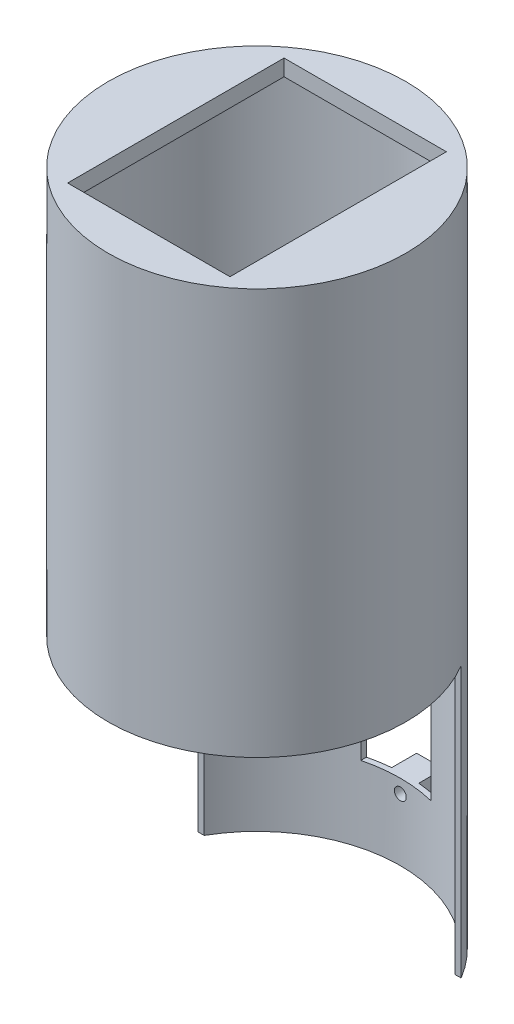
SolidWorks part; units mm, degrees
ref_plane "前基準面" through (0, 0, 0) normal (0, 0, 1) x (1, 0, 0)
ref_plane "上基準面" through (0, 0, 0) normal (0, 1, 0) x (1, 0, 0)
ref_plane "右基準面" through (0, 0, 0) normal (1, 0, 0) x (0, 0, -1)
sketch "草圖1" plane through (0, 0, 0) normal (0, 1, 0) x (1, 0, 0)
  circle A0 centre (0, 0) radius 27.5
  circle A1 centre (0, 0) radius 26.5
  dimension "D1" = 55
  dimension "D2" = 53
extrude "填料-伸長1" add sketch "草圖1" along normal blind 75 and the other way blind 50 contours A0
ref_plane "平面3" through (0, -10, 0) normal (0, 1, 0) x (1, 0, 0)
sketch "草圖8" plane through (0, 0, 0) normal (0, 1, 0) x (1, 0, 0)
  line L0 (0, 27.5) -> (0, -27.5) construction
  line L1 (14, 20.8205) -> (-14, 20.8205)
  line L2 (-14, 20.8205) -> (-14, -20.1795)
  line L3 (-14, -20.1795) -> (14, -20.1795)
  line L4 (14, 20.8205) -> (14, -20.1795)
  circle A1 centre (0, 0) radius 27.5 construction
  point P11 (0, -20.1795)
  point P12 (0, 20.8205)
  dimension "D1" = 28
  dimension "D2" = 41
sketch "草圖10" plane through (0, 75, 0) normal (0, 1, 0) x (1, 0, 0)
  line L0 (0, 27.5) -> (0, -27.5) construction
  line L10 (-27.5, 0) -> (27.5, 0) construction
  line L11 (-30.25, 0) -> (30.25, 0) construction
  line L12 (-15, 20) -> (-15, -20)
  line L13 (-15, 20) -> (15, 20)
  line L15 (-15, -20) -> (15, -20)
  line L16 (15, 20) -> (15, -20)
  circle A0 centre (0, 0) radius 27.5 construction
  dimension "D2" = 40
extrude "除料-伸長8" cut sketch "草圖10" against normal blind 45.1
ref_plane "平面4" through (0, 0, -37) normal (0, 0, 1) x (1, 0, 0)
extrude "除料-伸長9" cut sketch "草圖10<2>" against normal blind 113 and the other way blind 10
sketch "草圖10<2>" plane through (0, 75, 0) normal (0, 1, 0) x (1, 0, 0) same geometry as "草圖10"
sketch "草圖11" plane through (0, 0, 0) normal (0, 1, 0) x (1, 0, 0)
  line L0 (23.588, 14.1371) -> (-24.132, 13.1869)
  arc A0 (-24.132, 13.1869) -> (23.588, 14.1371) centre (0, 0) ccw
  circle A1 centre (0, 0) radius 27.5 construction
extrude "除料-伸長10" cut sketch "草圖11" against normal blind 54
sketch "草圖12" plane through (0, 0, 0) normal (0, 1, 0) x (1, 0, 0)
  line L0 (0, 27.5) -> (0, -27.5) construction
  circle A0 centre (0, 0) radius 26.5
  dimension "D1" = 53
extrude "除料-伸長11" cut sketch "草圖12" against normal blind 55 and the other way blind 72
sketch "草圖13" plane through (0, 0, 0) normal (0, 0, 1) x (1, 0, 0)
  line L0 (0, 0) -> (0, -54.6017) construction
  line L1 (-24.132, -25) -> (22.4286, -25) construction
  line L2 (-24.132, -50) -> (-24.132, 0) construction
  line L3 (22.4286, -50) -> (22.4286, 0) construction
  line L5 (-6.5, -12.5) -> (6.5, -12.5)
  line L6 (-6.5, -12.5) -> (-6.5, -36)
  line L7 (-6.5, -36) -> (6.5, -36)
  line L8 (6.5, -12.5) -> (6.5, -36)
  dimension "D1" = 13
  dimension "D2" = 23.5
  dimension "D3" = 6.5
  dimension "D4" = 12.5
extrude "除料-伸長12" cut sketch "草圖13" against normal blind 54
ref_plane "平面5" through (0, 0, -28) normal (0, 0, 1) x (1, 0, 0)
sketch "草圖14" plane through (0, 0, -28) normal (0, 0, 1) x (1, 0, 0)
  line L0 (0, -12.5) -> (0, -38.2336) construction
  line L1 (-6.5, -12.5) -> (6.5, -12.5) construction
  line L7 (6.5, -24.25) -> (-6.5, -24.25) construction
  line L8 (6.5, -12.5) -> (6.5, -36) construction
  line L9 (-6.5, -36) -> (-6.5, -12.5) construction
  line L10 (2.5, -36) -> (-2.5, -36)
  line L11 (2.5, -7.5) -> (-2.5, -7.5)
  line L12 (2.5, -7.5) -> (2.5, -12.5)
  line L13 (2.5, -12.5) -> (-2.5, -12.5)
  line L14 (-2.5, -7.5) -> (-2.5, -12.5)
  line L15 (-2.5, -41) -> (-2.5, -36)
  line L16 (2.5, -41) -> (-2.5, -41)
  line L17 (2.5, -41) -> (2.5, -36)
  dimension "D1" = 5
  dimension "D2" = 5
  dimension "D3" = 2.5
extrude "填料-伸長2" add sketch "草圖14" against normal blind 4 and the other way blind 1
sketch "草圖15" plane through (0, 0, -28) normal (0, 0, 1) x (1, 0, 0)
  line L0 (6.5, -24.25) -> (-6.5, -24.25) construction
  line L3 (6.5, -12.5) -> (6.5, -36) construction
  line L4 (-6.5, -36) -> (-6.5, -12.5) construction
  line L5 (30.25, -10) -> (-30.25, -10) construction
  circle A2 centre (0, -10) radius 1.1
  circle A3 centre (0, -38.5) radius 1.1
  dimension "D1" = 2.2
extrude "除料-伸長13" cut sketch "草圖15" against normal blind 5 and the other way blind 4
